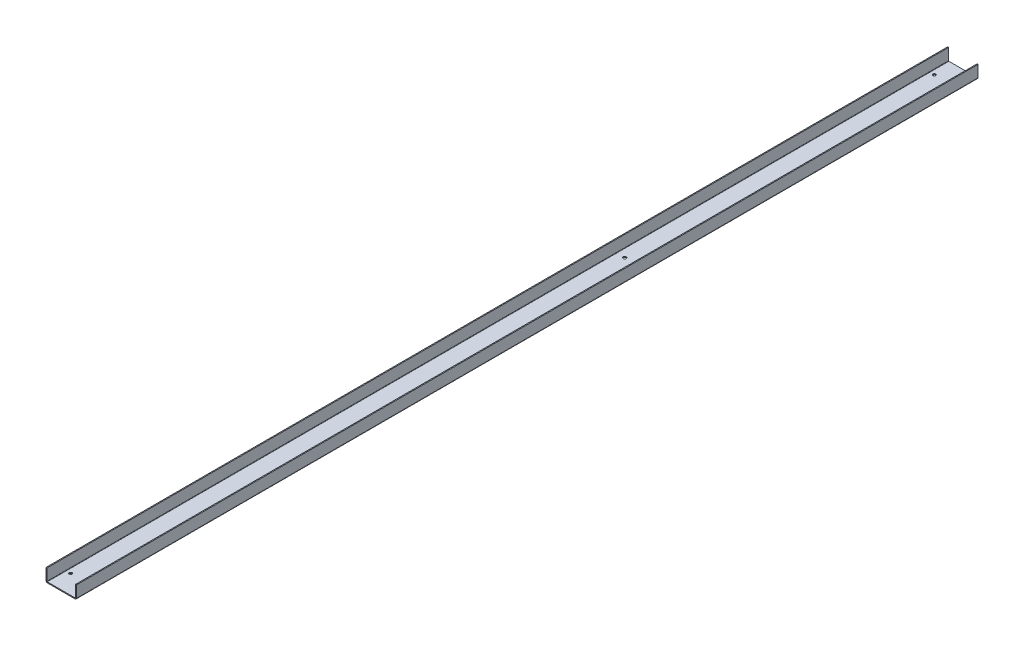
SolidWorks part; units mm, degrees
note: The reader was unsure of these and kept them because the rebuilt part matched: thickness of "基体-法兰1", "钣金8", "钣金9", "钣金10"; bend radius of "基体折弯1", "基体折弯2".
material "A3钢"
ref_plane "前视基准面" through (0, 0, 0) normal (0, 0, 1) x (1, 0, 0)
ref_plane "上视基准面" through (0, 0, 0) normal (0, 1, 0) x (1, 0, 0)
ref_plane "右视基准面" through (0, 0, 0) normal (1, 0, 0) x (0, 0, -1)
sketch "草图1" plane through (0, 0, 0) normal (0, 0, 1) x (1, 0, 0)
  line L0 (0, 37.5664) -> (0, -37.5664) construction
  line L1 (-30, 25) -> (-30, 0)
  line L2 (-30, 0) -> (30, 0)
  line L3 (30, 0) -> (30, 25)
  dimension "D1" = 60
  dimension "D2" = 25
base flange "基体-法兰1" sketch "草图1" end condition mid plane depth 1900 reverse direction no thickness 2 reverse thickness direction no bend radius 0.7366
bend "基体折弯1" bend radius 0.7366 bend angle 90 parameters "D5"=1
bend "基体折弯2" bend radius 0.7366 bend angle 90 parameters "D5"=2
sketch "草图6" plane through (0, 0, 0) normal (0, 1, 0) x (1, 0, 0)
  line L0 (-307.971, 0) -> (354.6332, 0) construction
  line L1 (0, 1155.6688) -> (0, -1099.6741) construction
  line L3 (-20, -910) -> (20, -910)
  line L4 (-20, -910) -> (-20, 910)
  line L5 (-20, 910) -> (20, 910)
  line L6 (20, -910) -> (20, 910)
  line L7 (-20, -910) -> (20, 910) construction
  line L8 (-20, 910) -> (20, -910) construction
  point P5 (0, 0)
  dimension "D1" = 40
  dimension "D2" = 1820
hole_wizard "Ø6.0 (6) 直径孔1" positions "3D草图1" profile "草图8" hole size "Ø6.0" standard "GB"
sketch3d "3D草图1"
  point P0 (-20, 0, -910)
  point P3 (20, 0, -910)
  point P6 (-20, 0, 910)
  point P9 (20, 0, 910)
sketch "草图8" plane through (-20, 0, -910) normal (1, 0, 0) x (0, 0, 1)
  line L0 (0, 0) -> (0, 16.8026)
  line L1 (0, 16.8026) -> (3, 15)
  line L2 (3, 15) -> (3, 0)
  line L5 (3, 0) -> (0, 0)
  line L10 (0, 16.8026) -> (-3, 15) construction
  line L11 (0, -6.35) -> (0, 107.95) construction
  dimension "孔直径" = 6
  dimension "孔深度" = 15
  dimension "导头角度" = 118
sketch "草图9" plane through (0, 0, 0) normal (0, 1, 0) x (1, 0, 0)
  line L0 (0, 376.2423) -> (0, -107.6343) construction
  line L1 (12.5, 250) -> (-12.5, 250) construction
  line L2 (-29.2634, 950) -> (29.2634, 950) construction
  point P7 (0, 0)
  dimension "D1" = 25
  dimension "D2" = 700
hole_wizard "Ø6.5 (6.5) 直径孔1" positions "3D草图2" profile "草图10" hole size "Ø6.5" standard "GB" end condition through all
sketch3d "3D草图2"
  point P0 (-12.5, 0, -250)
  point P3 (12.5, 0, -250)
sketch "草图10" plane through (-12.5, 0, -250) normal (1, 0, 0) x (0, 0, 1)
  line L0 (0, 0) -> (0, 2)
  line L1 (0, 2) -> (3.25, 2)
  line L2 (3.25, 2) -> (3.25, 0)
  line L5 (3.25, 0) -> (0, 0)
  line L11 (0, -6.35) -> (0, 107.95) construction
  dimension "通孔孔直径" = 6.5
  dimension "通孔孔深度" = 2
sketch "折弯-线1" [suppressed] plane through (0, 0, 0) normal (0, 1, 0) x (1, 0, 0)
sketch "边界框1" [suppressed] plane through (0, 0, 0) normal (0, 1, 0) x (1, 0, 0)
sheet metal parameters "钣金8" thickness 2 parameters "D1"=0.7366
flat pattern "平板型式8" [suppressed]
sketch "折弯-线2" plane through (0, 0, 0) normal (0, 1, 0) x (1, 0, 0)
  line L0 (-35.6273, -950) -> (-35.6273, 950) construction
  line L1 (35.6273, 950) -> (35.6273, -950) construction
  line L2 (-35.6273, -950) -> (-35.6273, 950) construction
  line L3 (35.6273, 950) -> (35.6273, -950) construction
sketch3d "边界框2" [suppressed]
  line L0 (-26.2546, 0, 0) -> (-26.2546, 1900, 0) construction
  line L1 (96.2546, 0, 0) -> (96.2546, 1900, 0) construction
  line L2 (-26.2546, 0, 0) -> (96.2546, 0, 0) construction
  line L3 (-26.2546, 1900, 0) -> (96.2546, 1900, 0) construction
bend of the flat pattern "展开-<基体折弯1>1"
bend of the flat pattern "展开-<基体折弯2>1"
sheet metal parameters "钣金9" thickness 2 parameters "D1"=0.7366
flat pattern "平板型式8"
sketch "折弯-线2" plane through (0, 0, 0) normal (0, 1, 0) x (1, 0, 0)
  line L0 (-30.6273, -950) -> (-30.6273, 950) construction
  line L1 (30.6273, 950) -> (30.6273, -950) construction
  line L2 (-30.6273, -950) -> (-30.6273, 950) construction
  line L3 (30.6273, 950) -> (30.6273, -950) construction
sketch3d "边界框2" [suppressed]
  line L0 (-26.2546, 0, 0) -> (-26.2546, 1900, 0) construction
  line L1 (86.2546, 0, 0) -> (86.2546, 1900, 0) construction
  line L2 (-26.2546, 0, 0) -> (86.2546, 0, 0) construction
  line L3 (-26.2546, 1900, 0) -> (86.2546, 1900, 0) construction
bend of the flat pattern "展开-<基体折弯1>1"
bend of the flat pattern "展开-<基体折弯2>1"
sheet metal parameters "钣金10" thickness 2 parameters "D1"=0.7366
flat pattern "平板型式8"
sketch "折弯-线2" plane through (0, 0, 0) normal (0, 1, 0) x (1, 0, 0)
  line L0 (-30.6273, -950) -> (-30.6273, 950) construction
  line L1 (30.6273, 950) -> (30.6273, -950) construction
  line L2 (-30.6273, -950) -> (-30.6273, 950) construction
  line L3 (30.6273, 950) -> (30.6273, -950) construction
sketch3d "边界框2" [suppressed]
  line L0 (-26.2546, 0, 0) -> (-26.2546, 1900, 0) construction
  line L1 (86.2546, 0, 0) -> (86.2546, 1900, 0) construction
  line L2 (-26.2546, 0, 0) -> (86.2546, 0, 0) construction
  line L3 (-26.2546, 1900, 0) -> (86.2546, 1900, 0) construction
bend of the flat pattern "展开-<基体折弯1>1"
bend of the flat pattern "展开-<基体折弯2>1"
